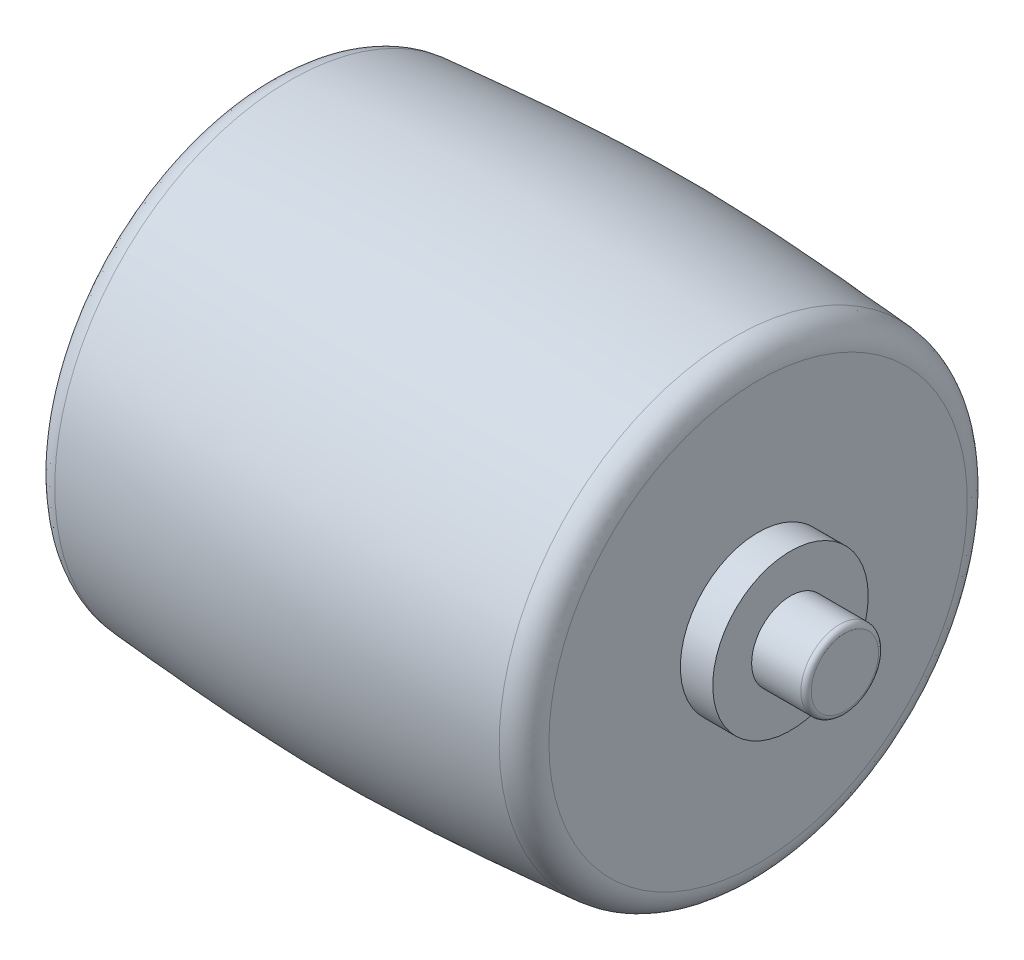
SolidWorks part; units mm, degrees
material "ｺﾞﾑ"
ref_plane "正面" through (0, 0, 0) normal (0, 0, 1) x (1, 0, 0)
ref_plane "平面" through (0, 0, 0) normal (0, 1, 0) x (1, 0, 0)
ref_plane "右側面" through (0, 0, 0) normal (1, 0, 0) x (0, 0, -1)
sketch "ｽｹｯﾁ1" plane through (0, 0, 0) normal (1, 0, 0) x (0, 0, -1)
  circle A0 centre (0, 0) radius 9.5
  dimension "D1" = 19
ref_plane "平面1" through (9.5, 0, 0) normal (1, 0, 0) x (0, 0, -1)
ref_plane "平面2" through (-9.5, 0, 0) normal (1, 0, 0) x (0, 0, -1)
sketch "ｽｹｯﾁ2" plane through (9.5, 0, 0) normal (1, 0, 0) x (0, 0, -1)
  circle A0 centre (0, 0) radius 9
  dimension "D1" = 18
sketch "ｽｹｯﾁ3" plane through (-9.5, 0, 0) normal (1, 0, 0) x (0, 0, -1)
  circle A0 centre (0, 0) radius 9
  dimension "D1" = 18
loft "ﾛﾌﾄ1" add profiles "ｽｹｯﾁ3", "ｽｹｯﾁ1", "ｽｹｯﾁ2" connector at (-9.5, 5.6844, -6.9777) connector at (0, 5.9351, -7.4178) connector at (9.5, 5.68, -6.9812)
sketch "ｽｹｯﾁ5" plane through (0, 0, 0) normal (1, 0, 0) x (0, 0, -1)
  circle A0 centre (0, 0) radius 1.5
  dimension "D1" = 3
extrude "ﾎﾞｽ - 押し出し1" add sketch "ｽｹｯﾁ5" along normal mid plane 25.7
fillet "ﾌｨﾚｯﾄ1" radius 1 2 edges at (9.5, 0, -9) (-9.5, 0, -9)
sketch "ｽｹｯﾁ6" plane through (0, 0, 0) normal (1, 0, 0) x (0, 0, -1)
  circle A0 centre (0, 0) radius 3
  dimension "D1" = 6
extrude "ﾎﾞｽ - 押し出し2" add sketch "ｽｹｯﾁ6" along normal mid plane 21.5
fillet "ﾌｨﾚｯﾄ3" radius 0.2 2 edges at (-12.85, 0, -1.5) (12.85, 0, -1.5)
